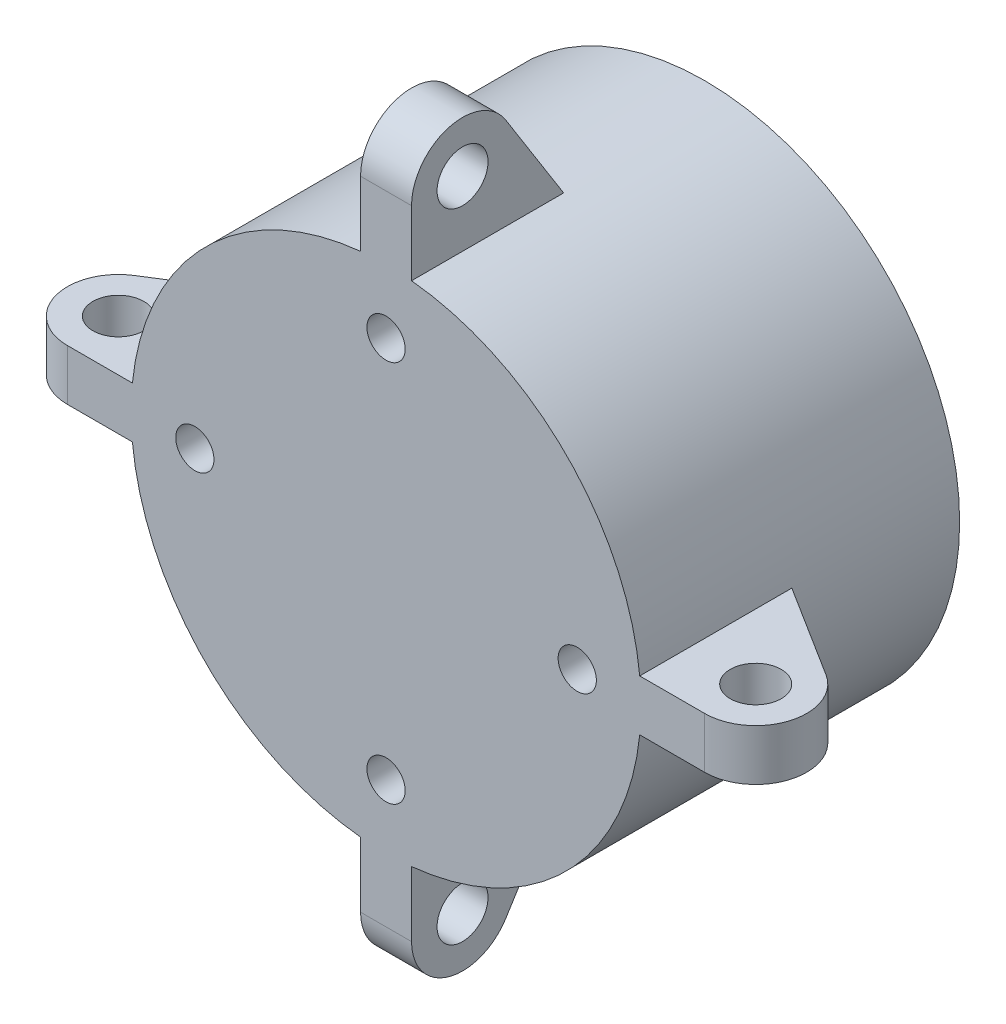
SolidWorks part; units mm, degrees
material "ABS"
ref_plane "前视基准面" through (0, 0, 0) normal (0, 0, 1) x (1, 0, 0)
ref_plane "上视基准面" through (0, 0, 0) normal (0, 1, 0) x (1, 0, 0)
ref_plane "右视基准面" through (0, 0, 0) normal (1, 0, 0) x (0, 0, -1)
sketch "草图1" plane through (0, 0, 0) normal (0, 0, 1) x (1, 0, 0)
  circle A0 centre (0, 0) radius 40
  dimension "D1" = 80
extrude "凸台-拉伸1" add sketch "草图1" against normal blind 50
sketch "草图2" plane through (0, 0, 0) normal (0, 0, 1) x (1, 0, 0)
  line L0 (0, 30) -> (0, 0) construction
  line L1 (0, 0) -> (0, -30) construction
  line L2 (-30, 0) -> (0, 0) construction
  line L3 (0, 0) -> (30, 0) construction
  circle A0 centre (0, 30) radius 3
  circle A1 centre (30, 0) radius 3
  circle A2 centre (0, -30) radius 3
  circle A3 centre (-30, 0) radius 3
  dimension "D1" = 6
  dimension "D2" = 6
  dimension "D3" = 6
  dimension "D4" = 6
  dimension "D5" = 30
  dimension "D6" = 30
  dimension "D7" = 30
  dimension "D8" = 30
extrude "切除-拉伸1" cut sketch "草图2" against normal blind 10
sketch "草图3" plane through (0, 0, 0) normal (1, 0, 0) x (0, 0, -1)
  line L0 (25, 38) -> (0, 38)
  line L1 (0, 38) -> (0, 50)
  line L2 (14.7716, 54.2598) -> (25, 38)
  line L3 (0, 40) -> (0, -40) construction
  arc A0 (0, 50) -> (14.7716, 54.2598) centre (8, 50) cw
  circle A1 centre (8, 50) radius 4
  dimension "D2" = 8
  dimension "D6" = 8
  dimension "D1" = 25
  dimension "D3" = 0
  dimension "D4" = 38
  dimension "D5" = 12
extrude "凸台-拉伸2" add sketch "草图3" along normal blind 4 and the other way blind 4
pattern_circular "阵列(圆周)1" count 4 every 90 about axis through (0, 0, -50) along (0, 0, 1) of "凸台-拉伸2"
